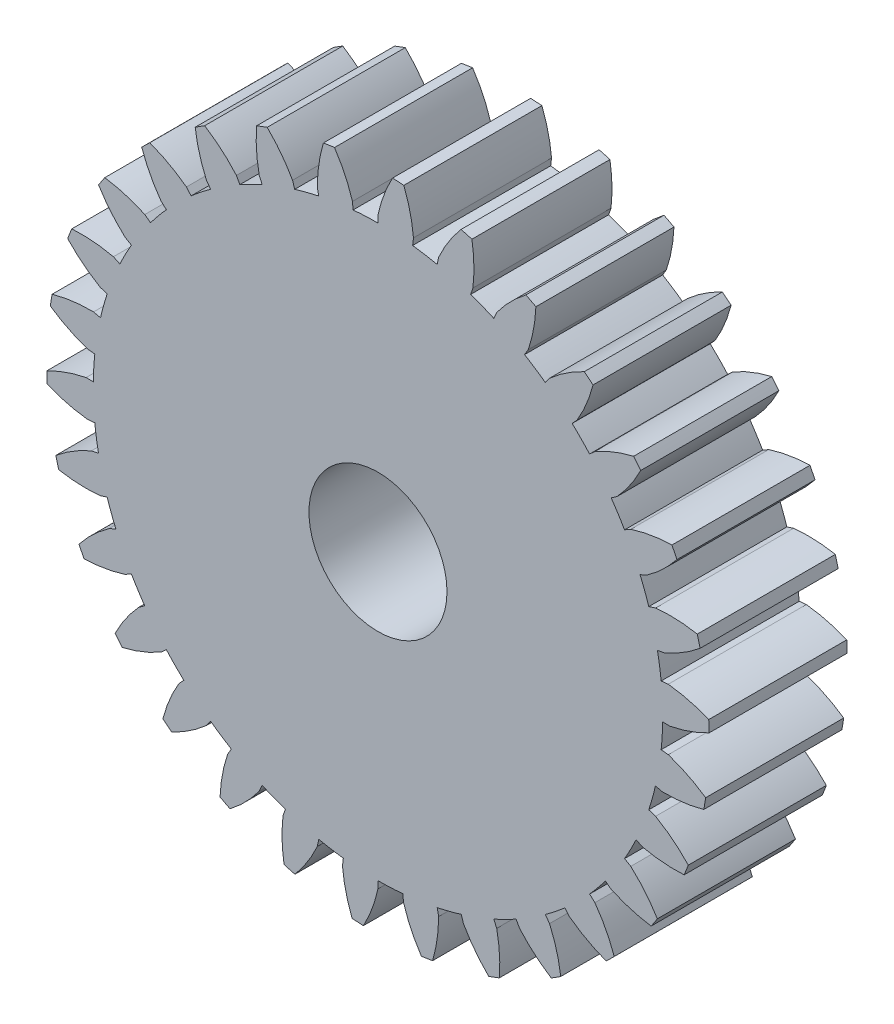
SolidWorks part; units mm, degrees
ref_plane "Front Plane" through (0, 0, 0) normal (0, 0, 1) x (1, 0, 0)
ref_plane "Top Plane" through (0, 0, 0) normal (0, 1, 0) x (1, 0, 0)
ref_plane "Right Plane" through (0, 0, 0) normal (1, 0, 0) x (0, 0, -1)
sketch "Gear" plane through (0, 0, 0) normal (0, 0, 1) x (1, 0, 0)
  circle A0 centre (0, 0) radius 9
  circle A1 centre (0, 0) radius 9.6
  circle A2 centre (0, 0) radius 8.25
  circle A3 centre (0, 0) radius 8.4
  circle A4 centre (0, 0) radius 8.4572
  dimension "Pitch" = 18
  dimension "Addendum" = 19.2
  dimension "Root" = 16.5
  dimension "Clearance" = 16.8
  dimension "Base" = 16.9145
sketch "Involute" plane through (0, 0, 0) normal (0, 0, 1) x (1, 0, 0)
  line L0 (0, 0) -> (0, 8.4572)
  line L1 (0, 0) -> (4.2286, 7.3242) construction
  line L2 (0, 0) -> (7.3242, 4.2286) construction
  line L3 (0, 0) -> (8.4572, 0) construction
  line L4 (8.4572, 0) -> (8.4572, 13.2846) construction
  line L5 (7.3242, 4.2286) -> (2.896, 11.8985) construction
  line L6 (4.2286, 7.3242) -> (0.3937, 9.5383) construction
  line L7 (0, 0) -> (0.9408, 8.9507) construction
  line L8 (0, 0) -> (1.8712, 8.8033)
  line L9 (0.5484, 8.9833) -> (0, 0) construction
  circle A0 centre (0, 0) radius 8.4572 construction
  circle A1 centre (0, 0) radius 9 construction
  arc A3 (0.9408, 8.9507) -> (0.155, 8.9987) centre (0, 0) ccw
  spline S0 degree 3 poles (0, 8.4572) (0.7439, 11.9206) (5.6033, 13.2891) (8.4572, 13.2846) knots 0 0 0 0 1 1 1 1
  spline S1 degree 3 poles (1.0288, 8.3944) (0.7117, 11.9226) (-3.9451, 13.872) (-6.7784, 14.2147) knots 0 0 0 0 1 1 1 1
  point P10 (0, 0)
  dimension "Involute Control" = 90
  dimension "Base Circle Quarter Circumference" = 13.2846
  dimension "D1" = 8.8564
  dimension "D2" = 4.4282
  dimension "Circular Pitch" = 12
  dimension "Involute Array" = 4
sketch "Sketch3" plane through (0, 0, 0) normal (0, 0, 1) x (1, 0, 0)
  line L0 (1.0288, 8.3944) -> (1.0036, 8.1887)
  line L2 (0, 8.4572) -> (0, 8.25)
  arc A2 (0.4218, 9.5907) -> (0, 8.4572) centre (4.1074, 7.574) ccw
  circle A10 centre (0, 0) radius 8.25 construction
  circle A11 centre (0, 0) radius 8.4572 construction
  arc A17 (1.0288, 8.3944) -> (0.748, 9.5708) centre (-3.1555, 8.0174) ccw
  arc A18 (1.0036, 8.1887) -> (0, 8.25) centre (0, 0) ccw
  arc A19 (0.748, 9.5708) -> (0.4218, 9.5907) centre (0, 0) ccw
  circle A20 centre (0, 0) radius 9.6 construction
  spline S1 degree 3 poles (1.0288, 8.3944) (0.7117, 11.9226) (-3.9451, 13.872) (-6.7784, 14.2147) knots 0 0 0 0 1 1 1 1 construction
  spline S2 degree 3 poles (0, 8.4572) (0.7439, 11.9206) (5.6033, 13.2891) (8.4572, 13.2846) knots 0 0 0 0 1 1 1 1 construction
extrude "Boss-Extrude1" add sketch "Sketch3" along normal blind 4
ref_axis "Axis1" through (0, 0, 0) along (0, 0, 1)
pattern_circular "CirPattern1" count 30 over 360 about axis through (0, 0, 0) along (0, 0, 1) of bodies 101
sketch "Sketch6" plane through (0, 0, 0) normal (0, 0, 1) x (1, 0, 0)
  circle A0 centre (0, 0) radius 8.25 construction
  circle A1 centre (0, 0) radius 8.25
  circle A2 centre (0, 0) radius 2
  dimension "D1" = 4
extrude "Boss-Extrude3" add sketch "Sketch6" along normal up to surface (4 mm away) up to face at (-1.2966, 8.6689, 4)
equation "\"Module\"= .6"
equation "\"Teeth\" = 30"
equation "\"Pressure Angle\"= 20deg"
equation "\"Pitch@Gear\"= \"Module\" * \"Teeth\""
equation "\"Addendum@Gear\" = \"Pitch@Gear\" +  ( \"Module\" * 2 ) "
equation "\"Clearance@Gear\" = \"Pitch@Gear\" - ( \"Module\" * 2 )"
equation "\"Root@Gear\"= \"Pitch@Gear\" - ( ( \"Module\" * 1.25 ) * 2 )"
equation "\"Base@Gear\"= \"Pitch@Gear\" * cos ( \"Pressure Angle\" )"
equation "\"Circular Pitch@Involute\"=360/\"Teeth\""
equation "\"Base Circle Quarter Circumference@Involute\"= \"Base@Gear\" * pi / 4"
equation "\"D1@Involute\"= \"Base Circle Quarter Circumference@Involute\" / 3 * 2"
equation "\"D2@Involute\"= \"Base Circle Quarter Circumference@Involute\" / 3"
equation "\"D1@CirPattern1\"= \"Teeth\""
